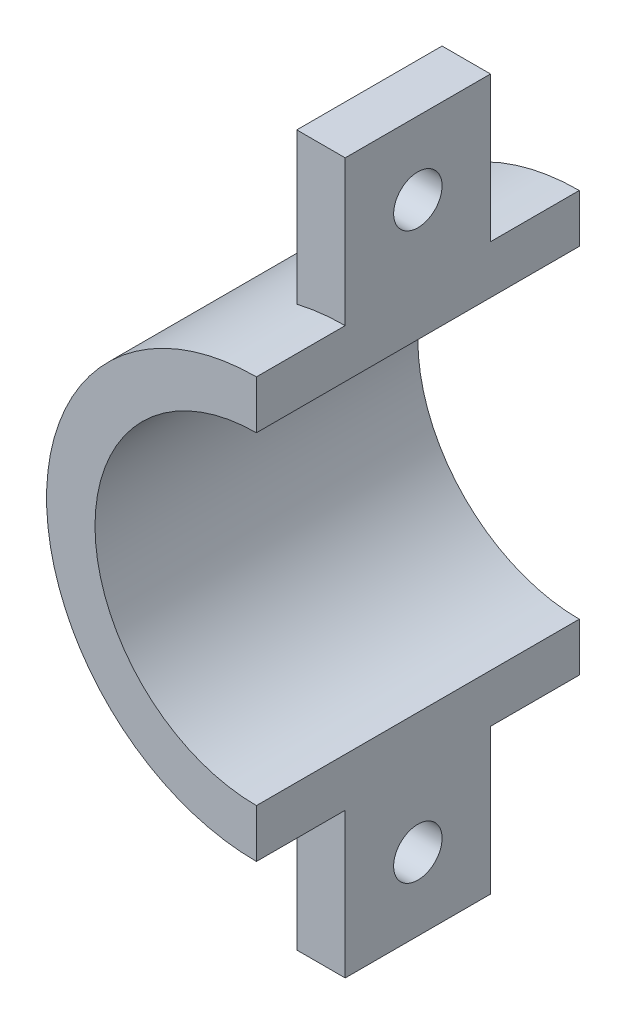
SolidWorks part; units mm, degrees
ref_plane "Спереди" through (0, 0, 0) normal (0, 0, 1) x (1, 0, 0)
ref_plane "Сверху" through (0, 0, 0) normal (0, 1, 0) x (1, 0, 0)
ref_plane "Справа" through (0, 0, 0) normal (1, 0, 0) x (0, 0, -1)
sketch "Эскиз1" plane through (0, 0, 0) normal (0, 0, 1) x (1, 0, 0)
  line L0 (0, 10) -> (0, 13)
  line L1 (0, -10) -> (0, -13)
  arc A0 (0, 10) -> (0, -10) centre (0, 0) ccw
  arc A1 (0, 13) -> (0, -13) centre (0, 0) ccw
  dimension "D1" = 10
  dimension "D3" = 20
  dimension "D2" = 3
extrude "Бобышка-Вытянуть1" add sketch "Эскиз1" along normal blind 20
sketch "Эскиз2" plane through (0, 0, 0) normal (1, 0, 0) x (0, 0, -1)
sketch "Эскиз3" plane through (0, 0, 0) normal (1, 0, 0) x (0, 0, -1)
  line L0 (-10, 10) -> (-10, -10) construction
  line L1 (-20, 10) -> (0, 10) construction
  line L2 (-20, -10) -> (0, -10) construction
  line L3 (-10, 10) -> (-14.5, 10)
  line L4 (-14.5, 10) -> (-14.5, 22)
  line L5 (-14.5, 22) -> (-5.5, 22)
  line L6 (-5.5, 22) -> (-5.5, 10)
  line L7 (-5.5, 10) -> (-10, 10)
  line L9 (-10, -10) -> (-14.5, -10)
  line L10 (-14.5, -10) -> (-14.5, -22)
  line L11 (-14.5, -22) -> (-5.5, -22)
  line L12 (-5.5, -22) -> (-5.5, -10)
  line L13 (-5.5, -10) -> (-10, -10)
  circle A0 centre (-10, 17.5) radius 1.5
  circle A1 centre (-10, -17.5) radius 1.5
  dimension "D1" = 3
  dimension "D2" = 4.5
  dimension "D3" = 7.5
  dimension "D4" = 12
  dimension "D5" = 4.5
  dimension "D6" = 7.5
  dimension "D7" = 4.5
extrude "Бобышка-Вытянуть2" add sketch "Эскиз3" against normal blind 3
